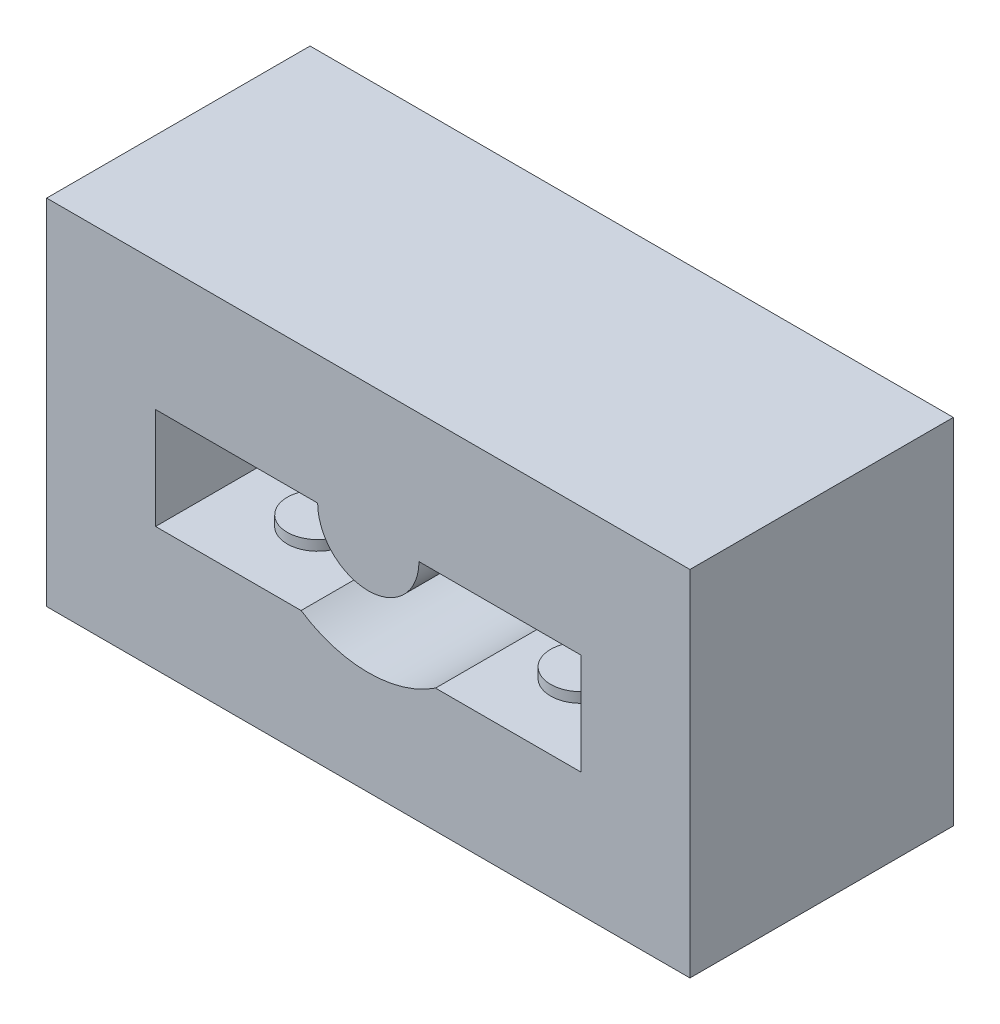
SolidWorks part; units mm, degrees
ref_plane "Front" through (0, 0, 0) normal (0, 0, 1) x (1, 0, 0)
ref_plane "Top" through (0, 0, 0) normal (0, 1, 0) x (1, 0, 0)
ref_plane "Right" through (0, 0, 0) normal (1, 0, 0) x (0, 0, -1)
sketch "Sketch1" plane through (0, 0, 0) normal (0, 0, 1) x (1, 0, 0)
  circle A0 centre (0, 0) radius 24
extrude "Extrude1" add sketch "Sketch1" along normal blind 5
sketch "Sketch2" plane through (0, 0, 5) normal (0, 0, 1) x (1, 0, 0)
  line L0 (-2.5, 0) -> (-10.5, 0)
  line L1 (2.5, 0) -> (10.5, 0)
  line L2 (10.5, 0) -> (10.5, -5)
  line L3 (10.5, -5) -> (-10.5, -5) construction
  line L4 (-10.5, -5) -> (-10.5, 0)
  line L5 (0, 0) -> (3.3166, -5) construction
  line L6 (0, 0) -> (-3.3166, -5) construction
  line L7 (-3.3166, -5) -> (-10.5, -5)
  line L8 (3.3166, -5) -> (10.5, -5)
  circle A0 centre (0, 0) radius 2.5 construction
  arc A1 (2.5, 0) -> (-2.5, 0) centre (0, 0) cw
  circle A2 centre (0, 0) radius 24
  circle A3 centre (0, 0) radius 6 construction
  arc A4 (3.3166, -5) -> (-3.3166, -5) centre (0, 0) cw
extrude "Extrude2" add sketch "Sketch2" along normal blind 8
sketch "Sketch7" plane through (0, 0, 0) normal (0, -1, 0) x (1, 0, 0)
  line L0 (10.5, 5) -> (2.5, 13) construction
  line L1 (24, 13) -> (-24, 13) construction
  line L2 (2.5, 13) -> (2.5, 5) construction
  line L3 (10.5, 13) -> (2.5, 5) construction
  line L4 (-10.5, 13) -> (-2.5, 5) construction
  line L5 (-2.5, 13) -> (-2.5, 5) construction
  line L7 (-2.5, 13) -> (-10.5, 5) construction
  circle A0 centre (-6.5, 9) radius 1.7
  circle A1 centre (6.5, 9) radius 1.7
  point P11 (6.5, 9)
  point P23 (-6.5, 9)
  dimension "D1" = 21
  dimension "D2" = 8
sketch "Sketch9" plane through (0, 0, 13) normal (0, 0, 1) x (1, 0, 0)
  line L0 (-15.875, 6.35) -> (15.875, 6.35)
  line L1 (15.875, 6.35) -> (15.875, -11.1125)
  line L2 (15.875, -11.1125) -> (-15.875, -11.1125)
  line L3 (-15.875, -11.1125) -> (-15.875, 6.35)
  circle A0 centre (0, 0) radius 24
extrude "Extrude4" cut sketch "Sketch9" against normal up to surface (13 mm away) up to face at (24, 0, 0)
sketch "Sketch10" plane through (0, 0, 13) normal (0, 0, 1) x (1, 0, 0)
  circle A0 centre (9.525, 3.175) radius 1.3
  circle A1 centre (-7.9375, 3.175) radius 1.3
  circle A2 centre (-7.9375, -7.9375) radius 1.5
  circle A3 centre (9.525, -7.9375) radius 1.5
  circle A4 centre (-3.175, 3.175) radius 1.4
  circle A5 centre (4.7625, 3.175) radius 1.4
sketch "Sketch11" plane through (0, -5, 0) normal (0, 1, 0) x (1, 0, 0)
  line L0 (-2.5, -13) -> (-10.5, -5) construction
  circle A0 centre (-6.5, -9) radius 1.5
  circle A1 centre (6.5, -9) radius 1.5
  point P0 (-10.2731, -5.2269)
  point P1 (-2.5, -13)
  point P4 (-2.5, -5)
  point P6 (-10.5, -13)
  point P8 (2.5, -5)
  point P10 (10.5, -13)
  point P12 (10.5, -5)
  point P14 (2.5, -13)
  point P16 (-6.5, -9)
  point P18 (6.5, -9)
extrude "Extrude6" add sketch "Sketch11" along normal blind 0.5
